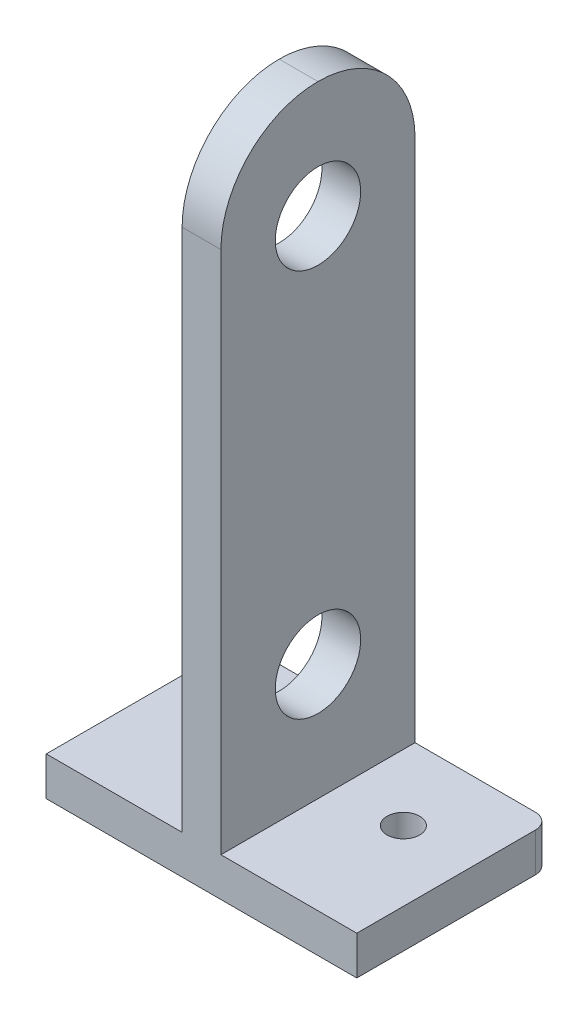
SolidWorks part; units mm, degrees
ref_plane "Front Plane" through (0, 0, 0) normal (0, 0, 1) x (1, 0, 0)
ref_plane "Top Plane" through (0, 0, 0) normal (0, 1, 0) x (1, 0, 0)
ref_plane "Right Plane" through (0, 0, 0) normal (1, 0, 0) x (0, 0, -1)
sketch "Sketch1" plane through (0, 0, 0) normal (0, 1, 0) x (1, 0, 0)
  line L1 (0, 0) -> (40, 0)
  line L2 (0, 0) -> (0, -25)
  line L3 (0, -25) -> (40, -25)
  line L4 (40, 0) -> (40, -25)
  dimension "D1" = 25
  dimension "D2" = 40
extrude "Boss-Extrude1" add sketch "Sketch1" along normal blind 5
sketch "Sketch3" plane through (0, 5, 0) normal (0, 1, 0) x (1, 0, 0)
  line L0 (40, 0) -> (0, 0) construction
  line L1 (17.5, 0) -> (22.5, 0)
  line L2 (17.5, 0) -> (17.5, -25)
  line L3 (17.5, -25) -> (22.5, -25)
  line L4 (22.5, 0) -> (22.5, -25)
  line L5 (0, -25) -> (40, -25) construction
  line L6 (0, 0) -> (0, -25) construction
  dimension "D1" = 5
  dimension "D2" = 17.5
extrude "Boss-Extrude2" add sketch "Sketch3" along normal blind 80
sketch "Sketch4" plane through (17.5, 0, 0) normal (-1, 0, 0) x (0, 0, 1)
  line L0 (0, 85) -> (0, 5) construction
  line L1 (0, 85) -> (25, 85) construction
  circle A0 centre (12.5, 70) radius 5.5
  circle A1 centre (12.5, 20) radius 5.5
  dimension "D1" = 11
  dimension "D2" = 11
  dimension "D3" = 50
  dimension "D4" = 12.5
  dimension "D5" = 15
extrude "Cut-Extrude1" cut sketch "Sketch4" against normal through all
sketch "Sketch7" plane through (0, 5, 0) normal (0, 1, 0) x (1, 0, 0)
  line L0 (17.5, 0) -> (0, 0) construction
  line L4 (0, 0) -> (0, -25) construction
  line L5 (40, -25) -> (40, 0) construction
  circle A0 centre (9, -10) radius 2.1
  circle A1 centre (31, -10) radius 2.1
  dimension "D1" = 4.2
  dimension "D2" = 4.2
  dimension "D3" = 10
  dimension "D4" = 9
  dimension "D5" = 9
extrude "Cut-Extrude2" cut sketch "Sketch7" against normal through all
fillet "Fillet1" radius 12.5 2 edges at (20, 85, 0) (20, 85, 25)
fillet "Fillet2" radius 2 2 edges at (0, 2.5, 0) (40, 2.5, 0)
